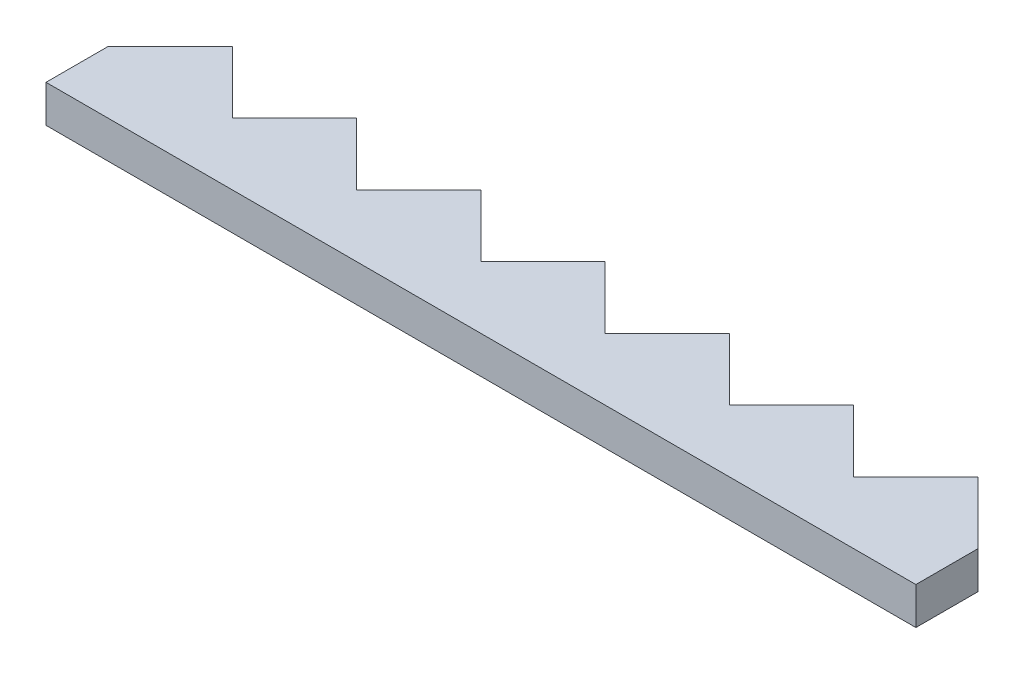
SolidWorks part; units mm, degrees
ref_plane "Front Plane" through (0, 0, 0) normal (0, 0, 1) x (1, 0, 0)
ref_plane "Top Plane" through (0, 0, 0) normal (0, 1, 0) x (1, 0, 0)
ref_plane "Right Plane" through (0, 0, 0) normal (1, 0, 0) x (0, 0, -1)
sketch "Sketch1" plane through (0, 0, 0) normal (0, 1, 0) x (1, 0, 0)
  line L0 (0, 5) -> (5, 10)
  line L2 (0, 5) -> (0, 0)
  line L3 (0, 0) -> (70, 0)
  line L5 (5, 10) -> (10, 5)
  line L6 (10, 5) -> (15, 10)
  line L7 (15, 10) -> (20, 5)
  line L8 (20, 5) -> (25, 10)
  line L9 (25, 10) -> (30, 5)
  line L10 (30, 5) -> (35, 10)
  line L11 (35, 10) -> (40, 5)
  line L12 (40, 5) -> (45, 10)
  line L13 (45, 10) -> (50, 5)
  line L14 (50, 5) -> (55, 10)
  line L15 (55, 10) -> (60, 5)
  line L16 (60, 5) -> (65, 10)
  line L17 (65, 10) -> (70, 5)
  line L18 (5, 10) -> (65, 10) construction
  line L19 (70, 5) -> (70, 0)
  dimension "D1" = 5
  dimension "D2" = 10
  dimension "D4" = 10
  dimension "D5" = 7
extrude "Boss-Extrude1" add sketch "Sketch1" along normal blind 3
